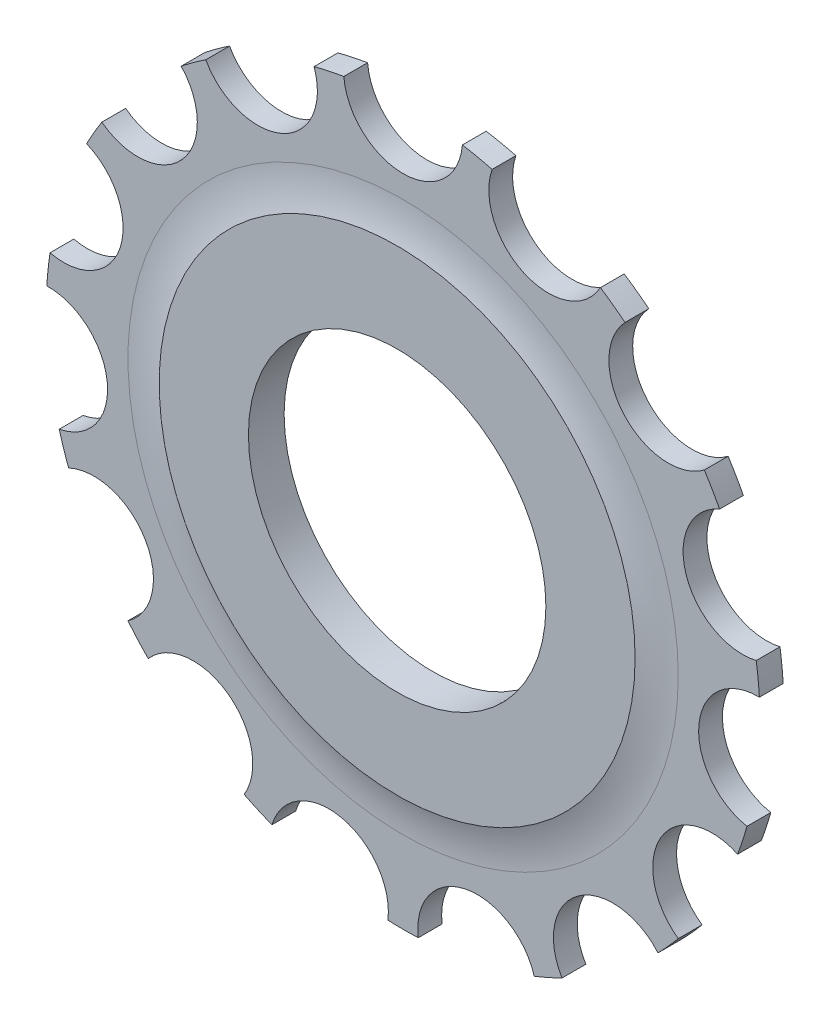
SolidWorks part; units mm, degrees
ref_plane "Front Plane" through (0, 0, 0) normal (0, 0, 1) x (1, 0, 0)
ref_plane "Top Plane" through (0, 0, 0) normal (0, 1, 0) x (1, 0, 0)
ref_plane "Right Plane" through (0, 0, 0) normal (1, 0, 0) x (0, 0, -1)
sketch "Sketch1" plane through (0, 0, 0) normal (0, 0, 1) x (1, 0, 0)
  arc A0 (-4.9826, 29.5833) -> (-7.4808, 29.0523) centre (0, 0) ccw
  arc A1 (-4.9826, 29.5833) -> (4.9826, 29.5833) centre (0, 30) ccw
  arc A2 (7.4808, 29.0523) -> (16.5845, 24.9991) centre (12.2021, 27.4064) ccw
  arc A3 (18.6507, 23.4979) -> (25.3187, 16.0923) centre (22.2943, 20.0739) ccw
  arc A4 (26.5957, 13.8805) -> (29.6751, 4.403) centre (28.5317, 9.2705) ccw
  arc A5 (29.9421, 1.863) -> (28.9004, -8.0476) centre (29.8357, -3.1359) ccw
  arc A6 (28.1112, -10.4766) -> (23.1286, -19.1067) centre (25.9808, -15) ccw
  arc A7 (21.4197, -21.0047) -> (13.3576, -26.8621) centre (17.6336, -24.2705) ccw
  arc A8 (11.0244, -27.9009) -> (1.277, -29.9728) centre (6.2374, -29.3444) ccw
  arc A9 (-1.277, -29.9728) -> (-11.0244, -27.9009) centre (-6.2374, -29.3444) ccw
  arc A10 (-13.3576, -26.8621) -> (-21.4197, -21.0047) centre (-17.6336, -24.2705) ccw
  arc A11 (-23.1286, -19.1067) -> (-28.1112, -10.4766) centre (-25.9808, -15) ccw
  arc A12 (-28.9004, -8.0476) -> (-29.9421, 1.863) centre (-29.8357, -3.1359) ccw
  arc A13 (-29.6751, 4.403) -> (-26.5957, 13.8805) centre (-28.5317, 9.2705) ccw
  arc A14 (-25.3187, 16.0923) -> (-18.6507, 23.4979) centre (-22.2943, 20.0739) ccw
  arc A15 (-16.5845, 24.9991) -> (-7.4808, 29.0523) centre (-12.2021, 27.4064) ccw
  arc A16 (-16.5845, 24.9991) -> (-18.6507, 23.4979) centre (0, 0) ccw
  arc A17 (-25.3187, 16.0923) -> (-26.5957, 13.8805) centre (0, 0) ccw
  arc A18 (-29.6751, 4.403) -> (-29.9421, 1.863) centre (0, 0) ccw
  arc A19 (-28.9004, -8.0476) -> (-28.1112, -10.4766) centre (0, 0) ccw
  arc A20 (-23.1286, -19.1067) -> (-21.4197, -21.0047) centre (0, 0) ccw
  arc A21 (-13.3576, -26.8621) -> (-11.0244, -27.9009) centre (0, 0) ccw
  arc A22 (-1.277, -29.9728) -> (1.277, -29.9728) centre (0, 0) ccw
  arc A23 (11.0244, -27.9009) -> (13.3576, -26.8621) centre (0, 0) ccw
  arc A24 (21.4197, -21.0047) -> (23.1286, -19.1067) centre (0, 0) ccw
  arc A25 (28.1112, -10.4766) -> (28.9004, -8.0476) centre (0, 0) ccw
  arc A26 (29.9421, 1.863) -> (29.6751, 4.403) centre (0, 0) ccw
  arc A27 (26.5957, 13.8805) -> (25.3187, 16.0923) centre (0, 0) ccw
  arc A28 (18.6507, 23.4979) -> (16.5845, 24.9991) centre (0, 0) ccw
  arc A29 (7.4808, 29.0523) -> (4.9826, 29.5833) centre (0, 0) ccw
  circle A30 centre (0, 0) radius 12.5
  point P49 (0, 0)
  dimension "D1" = 60
  dimension "D2" = 10
  dimension "D4" = 25
  dimension "D3" = 15
extrude "Boss-Extrude1" add sketch "Sketch1" along normal mid plane 3
sketch "Sketch2" plane through (0, 0, 1.5) normal (0, 0, 1) x (1, 0, 0)
  circle A0 centre (0, 0) radius 40
  circle A1 centre (0, 0) radius 20
  dimension "D1" = 40
  dimension "D2" = 80
extrude "Cut-Extrude1" cut sketch "Sketch2" against normal blind 0.5
fillet "Fillet1" radius 10 1 edges at (20, 0, 1)
mirror "Mirror1" about plane through (0, 0, 0) normal (0, 0, 1) of "Fillet1", "Cut-Extrude1"
